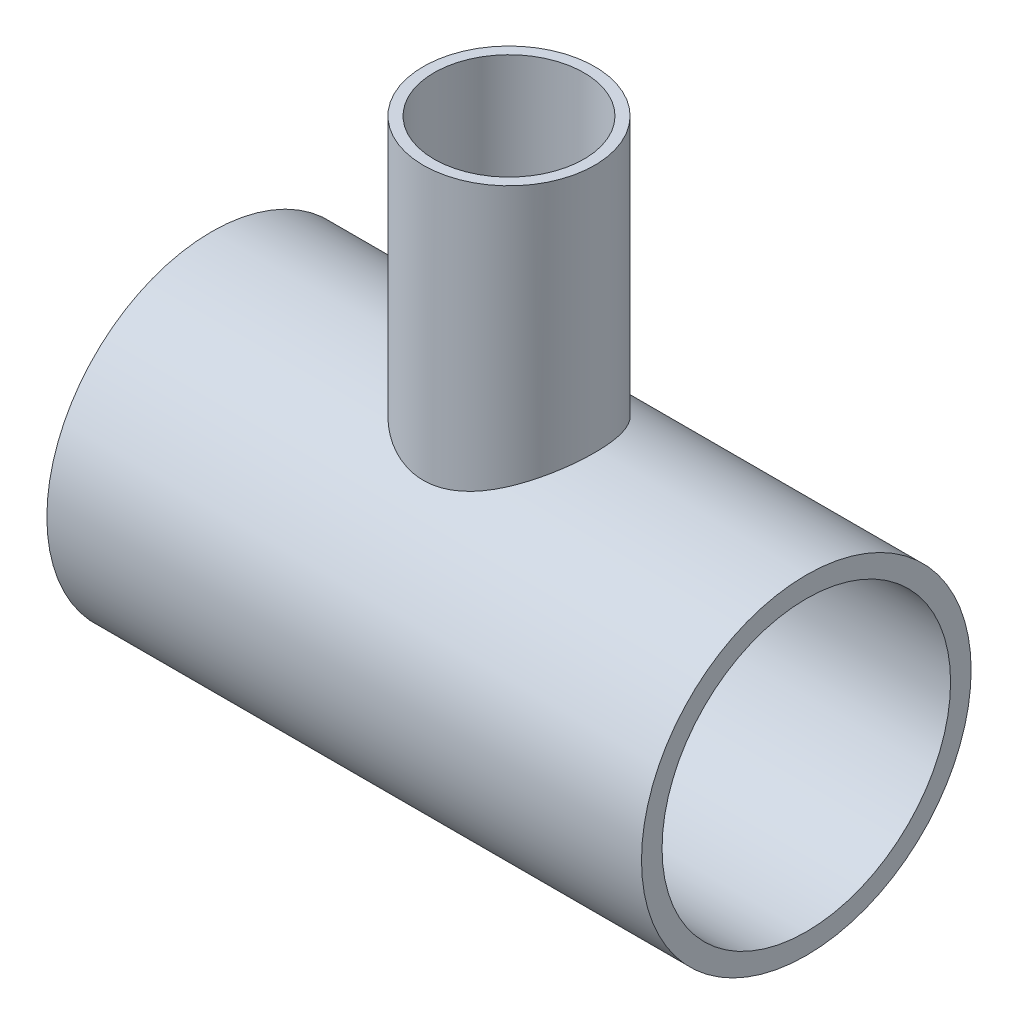
SolidWorks part; units mm, degrees
ref_plane "Front Plane" through (0, 0, 0) normal (0, 0, 1) x (1, 0, 0)
ref_plane "Top Plane" through (0, 0, 0) normal (0, 1, 0) x (1, 0, 0)
ref_plane "Right Plane" through (0, 0, 0) normal (1, 0, 0) x (0, 0, -1)
sketch "Revolve of 12 NOM" plane through (0, 0, 0) normal (0, 0, 1) x (1, 0, 0)
  line L0 (0, 0) -> (319.0916, 0) construction
  line L1 (0, 161.925) -> (584.2, 161.925)
  line L2 (0, 161.925) -> (0, 141.732)
  line L3 (0, 141.732) -> (584.2, 141.732)
  line L4 (584.2, 161.925) -> (584.2, 141.732)
  dimension "D1" = 141.732
  dimension "D2" = 161.925
  dimension "D3" = 584.2
revolve "Revolve12 NOM" add sketch "Revolve of 12 NOM" angle 360 about L0
ref_plane "Offset B Plane" through (0, 406.4, 0) normal (0, 1, 0) x (1, 0, 0)
sketch "Sketch2" plane through (0, 406.4, 0) normal (0, 1, 0) x (1, 0, 0)
  line L0 (-178.1175, 0) -> (178.1175, 0) construction
  line L1 (584.2, -161.925) -> (584.2, 161.925) construction
  circle A0 centre (292.1, 0) radius 84.1375
  dimension "D2" = 168.275
  dimension "D1" = 292.1
extrude "6 NOM OD Extrude" add sketch "Sketch2" against normal up to surface (268.0505 mm away) up to face at (0, 0, 161.925)
sketch "6 NOM ID Extrude" plane through (0, 406.4, 0) normal (0, 1, 0) x (1, 0, 0)
  circle A0 centre (292.1, 0) radius 73.6473
  dimension "D1" = 147.2946
extrude "6 NOM ID Extrude Cut" cut sketch "6 NOM ID Extrude" against normal up to surface (406.4 mm away) up to plane "Top Plane"
equation "\"A\"= 8in'EPG Datasheet"
equation "\"B\"= 16in'EPG Datasheet"
equation "\"L\"= 23in'EPG Datasheet"
equation "\"ID 12\"= 11.16in'EPG Datasheet"
equation "\"OD 12\"= 12.75in'EPG Datasheet"
equation "\"ID 6\"= 5.799in'EPG Datasheet"
equation "\"OD 6\"= 6.625in'EPG Datasheet"
equation "\"D1@Revolve of 12 NOM\" = \"ID 12\" / 2"
equation "\"D2@Revolve of 12 NOM\" = \"OD 12\" / 2"
equation "\"D3@Revolve of 12 NOM\" = \"L\""
equation "\"D1@Sketch2\"=\"L\"/2"
equation "\"D2@Sketch2\"=\"OD 6\""
equation "\"D1@6 NOM ID Extrude\" = \"ID 6\""
